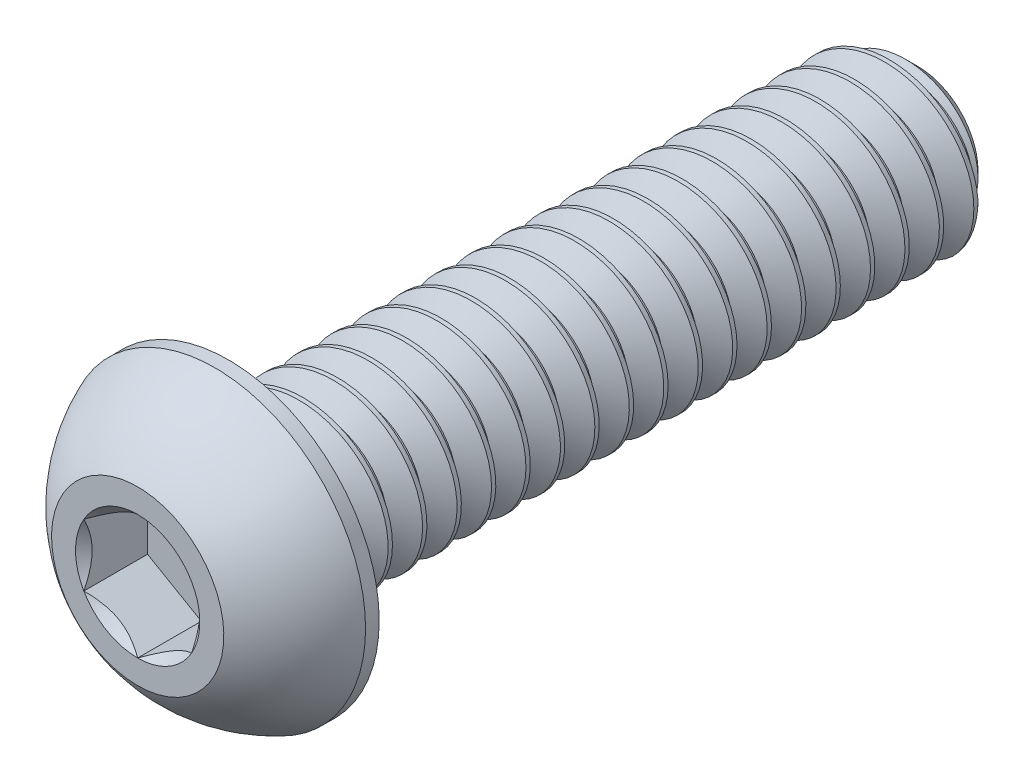
SolidWorks part; units mm, degrees
ref_plane "Front" through (0, 0, 0) normal (0, 0, 1) x (1, 0, 0)
ref_plane "Top" through (0, 0, 0) normal (0, 1, 0) x (1, 0, 0)
ref_plane "Right" through (0, 0, 0) normal (1, 0, 0) x (0, 0, -1)
sketch "Sketch1" plane through (0, 0, 0) normal (1, 0, 0) x (0, 0, -1)
  line L2 (3.3528, 3.175) -> (28.7528, 3.175)
  line L3 (28.7528, 3.175) -> (28.7528, 0)
  line L4 (28.7528, 0) -> (3.3528, 0)
  line L6 (2.8499, 5.5499) -> (3.3528, 5.5499) construction
  line L7 (28.7528, 3.175) -> (28.7528, -3.175) construction
  line L8 (0, 0) -> (3.3528, 0) construction
  line L9 (3.3528, 5.5499) -> (3.3528, -5.5499) construction
  line L11 (3.3528, 3.175) -> (3.3528, 0)
  line L13 (0, 1.9844) -> (0, -1.9844) construction
  line L14 (0, 1.9844) -> (0, 3.175) construction
  arc A3 (0, 3.175) -> (2.8499, 5.5499) centre (5.0603, 0) cw construction
  dimension "D1" = 0.5029
revolve "Revolve1" add sketch "Sketch1" angle 360 mid plane about L4
sketch "Sketch3" plane through (0, 0, -28.7528) normal (0, 0, -1) x (-1, 0, 0)
  circle A0 centre (0, 0) radius 3.175
curve "Helix/Spiral1" pitch 1.27 height 26.67 turns 21
sketch "Sketch2" plane through (0, 0, 0) normal (1, 0, 0) x (0, 0, -1)
  line L0 (28.7528, 3.175) -> (29.864, 3.175)
  line L1 (29.864, 3.175) -> (29.3878, 2.3501)
  line L2 (29.3878, 2.3501) -> (29.229, 2.3501)
  line L3 (29.229, 2.3501) -> (28.7528, 3.175)
  line L4 (28.9909, 2.7626) -> (29.6259, 2.7626) construction
  dimension "D1" = 60
  dimension "D2" = 0.1588
  dimension "D3" = 0.635
chamfer "Chamfer1" distance 0.9525 angle 45 1 edges at (0, 3.175, -28.7528)
sweep "Cut-Sweep1" cut profiles "Sketch2" path "Helix/Spiral1" align with end faces yes
sketch "Sketch7" plane through (0, 0, 0) normal (1, 0, 0) x (0, 0, -1)
  line L6 (2.8499, 5.5499) -> (3.3528, 5.5499) construction
  line L8 (0, 0) -> (3.3528, 0) construction
  line L11 (3.3528, 5.5499) -> (3.3528, -5.5499) construction
  line L12 (2.8499, 5.5499) -> (3.3528, 5.5499)
  line L13 (0, 0) -> (3.3528, 0)
  line L14 (0, 1.9844) -> (0, -1.9844) construction
  line L15 (3.3528, 5.5499) -> (3.3528, 0)
  line L16 (0, 3.175) -> (0, 0)
  arc A2 (2.8499, 5.5499) -> (0, 3.175) centre (5.0603, 0) ccw construction
  arc A3 (2.8499, 5.5499) -> (0, 3.175) centre (5.0603, 0) ccw
revolve "Revolve2" add sketch "Sketch7" angle 360 mid plane about L13
sketch "Sketch5" plane through (0, 0, 0) normal (0, 0, 1) x (1, 0, 0)
  line L1 (1.9844, -1.1457) -> (1.9844, 1.1457)
  line L2 (1.9844, 1.1457) -> (0, 2.2914)
  line L3 (0, 2.2914) -> (-1.9844, 1.1457)
  line L4 (-1.9844, 1.1457) -> (-1.9844, -1.1457)
  line L5 (-1.9844, -1.1457) -> (0, -2.2914)
  line L6 (0, -2.2914) -> (1.9844, -1.1457)
  circle A0 centre (0, 0) radius 1.9844 construction
extrude "Cut-Extrude2" cut sketch "Sketch5" against normal blind 2.347
sketch "Sketch6" plane through (0, 0, 0) normal (0, 0, 1) x (1, 0, 0)
  circle A0 centre (0, 0) radius 2.2914
extrude "Cut-Extrude3" cut sketch "Sketch6" against normal blind 2.347 draft 45
sketch "Sketch9" [suppressed] plane through (0, 0, -3.3528) normal (0, 0, 1) x (1, 0, 0)
  circle A2 centre (0, 0) radius 3.175
extrude "Boss-Extrude2" [suppressed] add sketch "Sketch9" against normal offset from surface (25.4 mm away) 22.225
sketch "Sketch10" plane through (0, 0, 0) normal (1, 0, 0) x (0, 0, -1)
  line L0 (28.7528, 3.175) -> (28.7528, -3.175) construction
  point P0 (26.8478, -3.175)
  dimension "D1" = 1.905
equation "\"D3@Helix/Spiral1\" = \"Lg@Sketch1\" + \"D4@Helix/Spiral1\""
equation "\"D2@Sketch2\" = \"D4@Helix/Spiral1\" * .125"
equation "\"D3@Sketch2\" = \"D4@Helix/Spiral1\" * .5"
equation "\"D1@Chamfer1\" = \"D4@Helix/Spiral1\" * .75"
equation "\"D1@Cut-Extrude2\" = \"Head Ht@Sketch1\" * .7"
equation "\"D1@Sketch1\" = \"Head Ht@Sketch1\" * .15"
equation "\"D1@Sketch10\" = \"D4@Helix/Spiral1\" * 1.5"
equation "\"D1@Cut-Extrude3\" = \"D1@Cut-Extrude2\""
